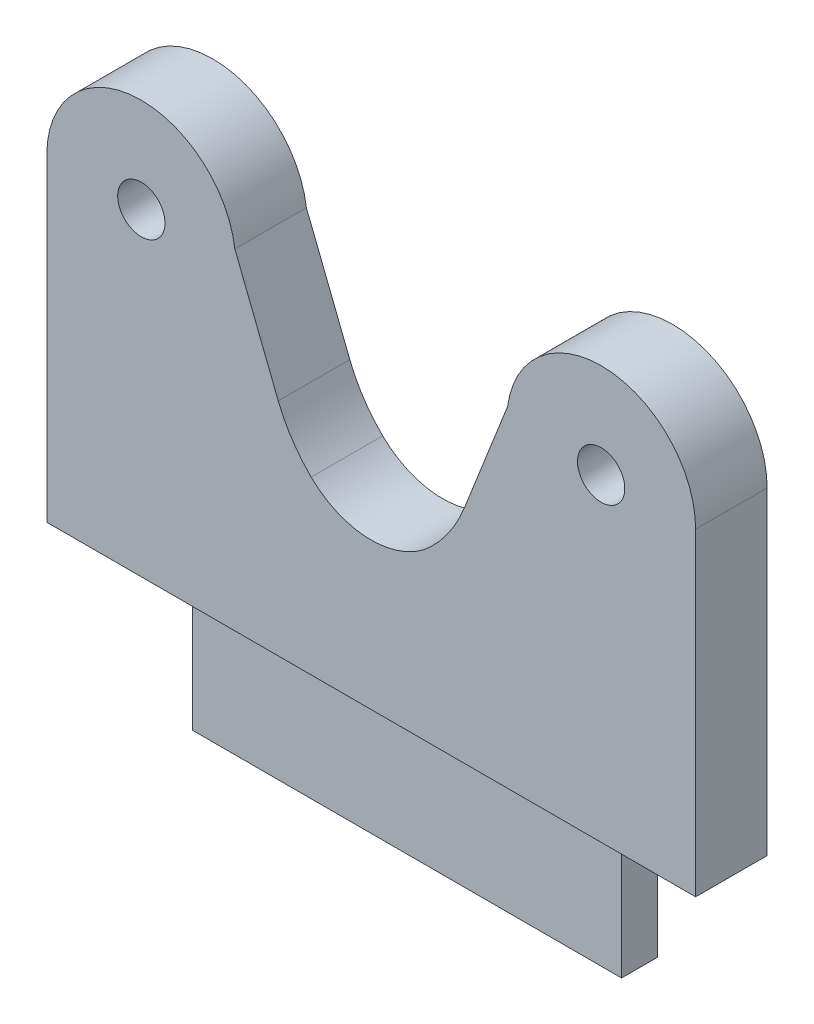
SolidWorks part; units mm, degrees
ref_plane "Plan de face" through (0, 0, 0) normal (0, 0, 1) x (1, 0, 0)
ref_plane "Plan de dessus" through (0, 0, 0) normal (0, 1, 0) x (1, 0, 0)
ref_plane "Plan de droite" through (0, 0, 0) normal (1, 0, 0) x (0, 0, -1)
sketch "Esquisse2" plane through (0, 0, 0) normal (0, 0, 1) x (1, 0, 0)
  line L5 (19.05, 0) -> (28.2948, 25.4)
  line L7 (5.08, 11.5764) -> (-5.08, 11.5764)
  line L10 (-19.05, 0) -> (-28.2948, 25.4)
  line L12 (-19.05, 0) -> (19.05, 0) construction
  line L13 (-5.08, 11.5764) -> (-12.1075, 29.3564)
  line L14 (5.08, 11.5764) -> (12.1075, 29.3564)
  line L17 (-19.05, 0) -> (-19.05, -12.7)
  line L18 (-19.05, -12.7) -> (19.05, -12.7)
  line L19 (19.05, 0) -> (19.05, -12.7)
  arc A5 (-28.2948, 25.4) -> (-12.1075, 29.3564) centre (-20.4183, 28.2668) cw
  arc A6 (28.2948, 25.4) -> (12.1075, 29.3564) centre (20.4183, 28.2668) ccw
  point P4 (0, 0)
  point P6 (0, 0)
  point P18 (0, 11.5764)
  dimension "D3" = 110
  dimension "D8" = 8.382
  dimension "D1" = 11.5764
  dimension "D2" = 10.16
  dimension "D4" = 110
  dimension "D5" = 38.1
  dimension "D6" = 17.78
  dimension "D7" = 12.7
  dimension "D9" = 25.4
  dimension "D12" = 10.16
extrude "Boss.-Extru.1" add sketch "Esquisse2" along normal mid plane 6.35
sketch "Esquisse3" plane through (0, 0, 3.175) normal (0, 0, 1) x (1, 0, 0)
  line L0 (-28.2948, 25.4) -> (-19.05, 0) construction
  circle A0 centre (-20.4102, 28.2445) radius 2.1
  arc A1 (-12.1075, 29.3564) -> (-28.2948, 25.4) centre (-20.4183, 28.2668) ccw construction
  dimension "D1" = 4.2
  dimension "D2" = 8.382
  dimension "D3" = 0.0238
extrude "Enlèv. mat.-Extru.1" cut sketch "Esquisse3" against normal through all
mirror "Symétrie1" about plane through (0, 0, 0) normal (1, 0, 0) of "Enlèv. mat.-Extru.1"
sketch "Esquisse4" plane through (0, 0, 3.175) normal (0, 0, 1) x (1, 0, 0)
  line L1 (-19.05, 0) -> (19.05, 0)
  line L2 (-19.05, 0) -> (-19.05, -12.7)
  line L3 (-19.05, -12.7) -> (19.05, -12.7)
  line L4 (19.05, 0) -> (19.05, -12.7)
extrude "Enlèv. mat.-Extru.2" cut sketch "Esquisse4" against normal blind 3.175
fillet "Congé1" radius 12.7 2 edges at (5.08, 11.5764, 0) (-5.08, 11.5764, 0)
fillet "Congé4" radius 7.62 1 edges at (0, 12.0845, 0)
fillet "Congé5" radius 15.24 2 edges at (19.05, 0, -1.5875) (-19.05, 0, -1.5875)
sketch "Esquisse6" plane through (0, 0, 0) normal (0, 0, 1) x (1, 0, 0)
  line L4 (28.8003, 28.2668) -> (28.8003, 0)
  line L5 (28.8003, 0) -> (19.2888, 0)
  line L6 (19.9691, 2.5252) -> (28.2948, 25.4) construction
  line L7 (19.9691, 2.5252) -> (28.2948, 25.4)
  arc A2 (28.2948, 25.4) -> (12.1075, 29.3564) centre (20.4183, 28.2668) ccw construction
  arc A3 (19.9691, 2.5252) -> (19.05, -2.6872) centre (34.29, -2.6872) ccw construction
  arc A4 (19.9691, 2.5252) -> (19.2888, 0) centre (34.29, -2.6872) ccw
  arc A5 (28.2948, 25.4) -> (28.8003, 28.2668) centre (20.4183, 28.2668) ccw
  dimension "D1" = 28.2668
  dimension "D2" = 9.5116
extrude "Boss.-Extru.4" add sketch "Esquisse6" against normal up to surface and the other way up to surface up to face at (18.3102, 28.2445, -3.175) other way up to face at (18.3102, 28.2445, 3.175)
mirror "Symétrie3" about plane through (0, 0, 0) normal (1, 0, 0) of "Boss.-Extru.4"
fillet "Congé6" radius 2.54 2 edges at (-19.2888, 0, -1.5875) (19.2888, 0, -1.5875)
sketch "Esquisse7" plane through (0, 0, 3.175) normal (0, 0, 1) x (1, 0, 0)
  line L0 (-19.2888, 0) -> (-19.05, 0)
  line L1 (-19.9691, 2.5252) -> (-19.05, 0) construction
  line L3 (-19.9691, 2.5252) -> (-19.05, 0)
  arc A0 (-19.2888, 0) -> (-19.9691, 2.5252) centre (-34.29, -2.6872) ccw construction
  arc A1 (-19.2888, 0) -> (-19.9691, 2.5252) centre (-34.29, -2.6872) ccw
extrude "Boss.-Extru.5" add sketch "Esquisse7" against normal through all
mirror "Symétrie4" about plane through (0, 0, 0) normal (1, 0, 0) of "Boss.-Extru.5"
